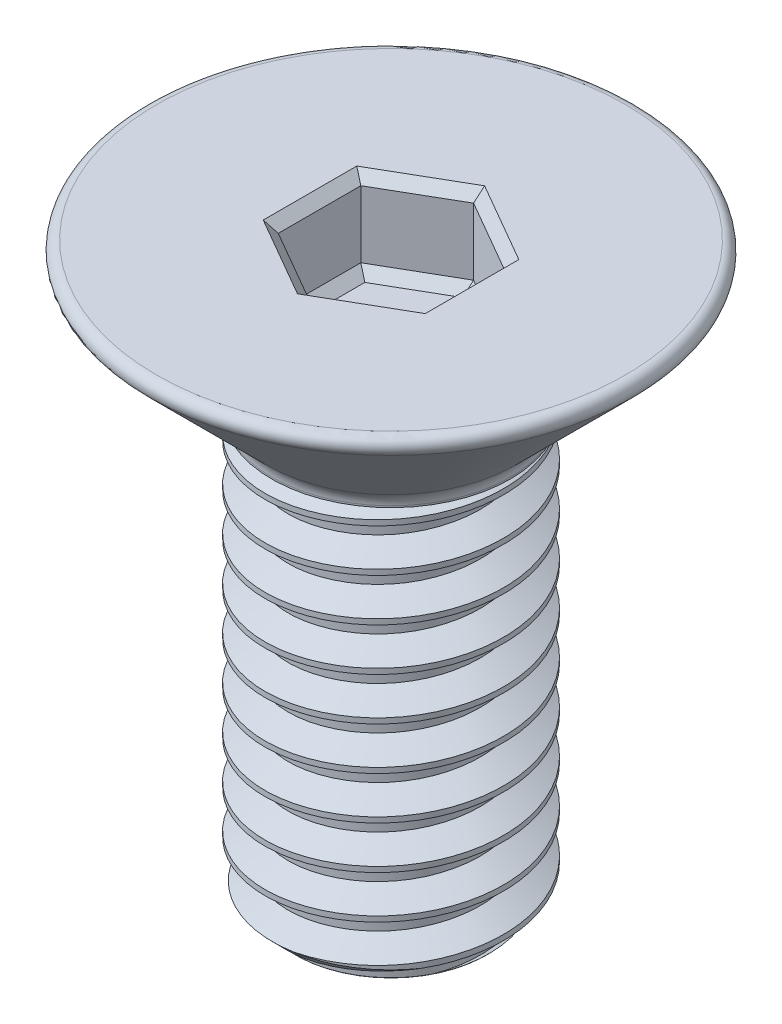
SolidWorks part; units mm, degrees
material "AISI Type A2 Tool Steel"
ref_plane "Front Plane" through (0, 0, 0) normal (0, 0, 1) x (1, 0, 0)
ref_plane "Top Plane" through (0, 0, 0) normal (0, 1, 0) x (1, 0, 0)
ref_plane "Right Plane" through (0, 0, 0) normal (1, 0, 0) x (0, 0, -1)
sketch "Sketch1" plane through (0, 0, 0) normal (0, 1, 0) x (1, 0, 0)
  circle A0 centre (0, 0) radius 1.25
  dimension "D1" = 2.5
extrude "Boss-Extrude1" add sketch "Sketch1" along normal blind 4.45
thread "Thread1" pitch 0.45 method cut profile "Thread Profile1" start angle 0, offset 1, length 0, pitch 0.45, diameter 2.5
ref_plane "Plane1" through (1.25, -1, 0) normal (0, 0, 1) x (1, 0, 0)
sketch "Thread Profile1" plane through (1.25, -1, 0) normal (0, 0, 1) x (1, 0, 0)
  line L0 (0, 0) -> (0, 0.45) construction
  line L11 (0, 0) -> (0, 0.3937)
  line L12 (0, 0.3937) -> (-0.2436, 0.2531)
  line L13 (-0.2436, 0.2531) -> (-0.2436, 0.1406)
  line L15 (-0.2436, 0.1406) -> (0, 0)
  line L17 (-0.2436, 0.1969) -> (0, 0.1969) construction
  point P2 (0, 0)
  dimension "Pitch" = 0.45
  dimension "Profile_Angle" = 60
  dimension "Profile_Land" = 0.1125
  dimension "Profile_Height" = 0.2436
sketch "Sketch5" plane through (0, 4.45, 0) normal (0, 1, 0) x (1, 0, 0)
  circle A0 centre (0, 0) radius 1.25
  dimension "D1" = 2.5
extrude "Boss-Extrude2" add sketch "Sketch5" along normal blind 0.1
sketch "Sketch6" plane through (0, 4.55, 0) normal (0, 1, 0) x (1, 0, 0)
  circle A0 centre (0, 0) radius 1.25
  dimension "D1" = 2.5
extrude "Boss-Extrude3" add sketch "Sketch6" along normal blind 1.45 draft 45 draft outward yes
fillet "Fillet1" radius 0.2 1 edges at (0, 4.55, 1.25)
fillet "Fillet2" radius 0.1 1 edges at (0, 6, 2.7)
sketch "Sketch7" plane through (0, 0, 0) normal (0, 0, 1) x (1, 0, 0)
  line L0 (0, 0) -> (0, 0.3237) construction
  line L1 (0, 0) -> (1.26, 0) construction
  line L2 (1.26, 0) -> (1.26, 0.26)
  line L3 (1.26, 0.26) -> (1, 0)
  line L4 (1, 0) -> (1.26, 0)
  dimension "D1" = 45
  dimension "D2" = 0.26
  dimension "D3" = 1.26
revolve "Cut-Revolve1" cut sketch "Sketch7" angle 360 about L0
sketch "Sketch8" plane through (0, 6, 0) normal (0, 1, 0) x (1, 0, 0)
  line L1 (0, 0.866) -> (-0.75, 0.433)
  line L2 (-0.75, 0.433) -> (-0.75, -0.433)
  line L3 (-0.75, -0.433) -> (0, -0.866)
  line L4 (0, -0.866) -> (0.75, -0.433)
  line L5 (0.75, -0.433) -> (0.75, 0.433)
  line L6 (0.75, 0.433) -> (0, 0.866)
  circle A0 centre (0, 0) radius 0.75 construction
  dimension "D1" = 1.5
extrude "Cut-Extrude1" cut sketch "Sketch8" against normal blind 0.8
chamfer "Chamfer1" distance 0.1 angle 45 6 edges at (-0.75, 6, 0) (-0.375, 6, 0.6495) (0.375, 6, 0.6495) (0.75, 6, 0) (0.375, 6, -0.6495) (-0.375, 6, -0.6495)
sketch "Sketch9" plane through (0, 5.2, 0) normal (0, 1, 0) x (1, 0, 0)
  line L1 (0, 0.866) -> (-0.75, 0.433)
  line L2 (-0.75, 0.433) -> (-0.75, -0.433)
  line L3 (-0.75, -0.433) -> (0, -0.866)
  line L4 (0, -0.866) -> (0.75, -0.433)
  line L5 (0.75, -0.433) -> (0.75, 0.433)
  line L6 (0.75, 0.433) -> (0, 0.866)
  circle A0 centre (0, 0) radius 0.75 construction
extrude "Cut-Extrude2" cut sketch "Sketch9" against normal blind 0.1 draft 45
